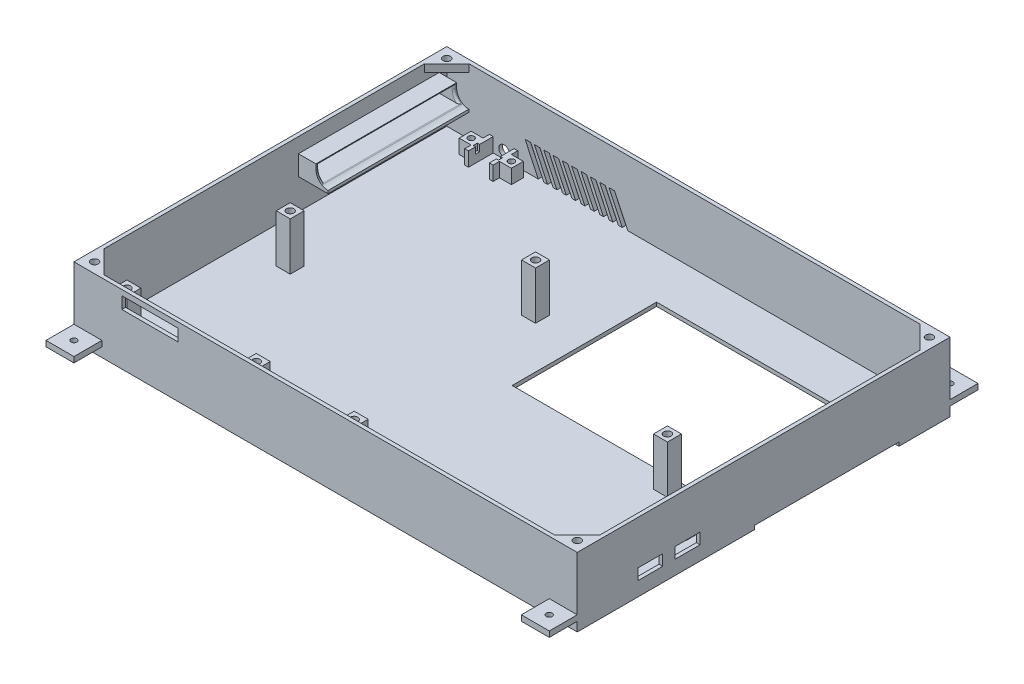
SolidWorks part; units mm, degrees
material "PLA"
ref_plane "Спереди" through (0, 0, 0) normal (0, 0, 1) x (1, 0, 0)
ref_plane "Сверху" through (0, 0, 0) normal (0, 1, 0) x (1, 0, 0)
ref_plane "Справа" through (0, 0, 0) normal (1, 0, 0) x (0, 0, -1)
sketch "Эскиз1" plane through (0, 0, 0) normal (0, 1, 0) x (1, 0, 0)
  line L1 (135, 100) -> (-135, 100)
  line L2 (135, 100) -> (135, -100)
  line L3 (135, -100) -> (-135, -100)
  line L4 (-135, 100) -> (-135, -100)
  line L5 (135, 100) -> (-135, -100) construction
  line L6 (135, -100) -> (-135, 100) construction
  point P0 (0, 0)
  dimension "D1" = 200
  dimension "D2" = 270
extrude "Бобышка-Вытянуть1" add sketch "Эскиз1" along normal blind 2
sketch "Эскиз2" plane through (0, 2, 0) normal (0, 1, 0) x (1, 0, 0)
  line L0 (133, 98) -> (-133, 98)
  line L1 (-133, 98) -> (-133, -98)
  line L2 (-133, -98) -> (-109.3, -98)
  line L3 (133, -98) -> (133, 98)
  line L4 (-135, 100) -> (-135, -100)
  line L5 (-135, -100) -> (135, -100)
  line L6 (135, -100) -> (135, 100)
  line L7 (135, 100) -> (-135, 100)
  line L8 (-135, 100) -> (-135, -100)
  line L9 (-135, -100) -> (-109.3, -100)
  line L10 (135, -100) -> (135, 100)
  line L11 (135, 100) -> (-135, 100)
  line L12 (-109.3, -98) -> (-109.3, -100)
  line L14 (-79.1, -98) -> (-79.1, -100)
  line L16 (-79.1, -98) -> (133, -98)
  line L17 (-79.1, -100) -> (135, -100)
  line L18 (-133, -98) -> (133, -98) construction
  line L20 (-135, -100) -> (135, -100) construction
  dimension "D3" = 25.7
  dimension "D4" = 55.9
  dimension "D1" = 0
  dimension "D2" = 2
extrude "Бобышка-Вытянуть2" add sketch "Эскиз2" along normal offset from surface (35 mm away) 8 offset beyond the face yes
sketch "Эскиз3" plane through (0, 2, 0) normal (0, 1, 0) x (1, 0, 0)
  line L1 (-109.3, -98) -> (-79.1, -98)
  line L2 (-109.3, -98) -> (-109.3, -100)
  line L3 (-109.3, -100) -> (-79.1, -100)
  line L4 (-79.1, -98) -> (-79.1, -100)
extrude "Бобышка-Вытянуть3" add sketch "Эскиз3" along normal blind 25.7
sketch "Эскиз4" plane through (-109.3, 0, 0) normal (1, 0, 0) x (0, 0, -1)
  line L0 (-100, 37) -> (-100, 27.7) construction
  line L1 (-98, 37) -> (-100, 37)
  line L2 (-98, 37) -> (-98, 34.1)
  line L3 (-98, 34.1) -> (-100, 34.1)
  line L4 (-100, 37) -> (-100, 34.1)
  dimension "D1" = 2.9
extrude "Бобышка-Вытянуть4" add sketch "Эскиз4" along normal up to surface (30.2 mm away) up to face at (-79.1, 32.35, 99)
sketch "Эскиз5" plane through (135, 0, 0) normal (1, 0, 0) x (0, 0, -1)
  line L0 (-100, 37) -> (-100, 0) construction
  line L1 (-54.15, 13.5) -> (-67.45, 13.5)
  line L2 (-54.15, 13.5) -> (-54.15, 7.6)
  line L3 (-54.15, 7.6) -> (-67.45, 7.6)
  line L4 (-67.45, 13.5) -> (-67.45, 7.6)
  line L5 (-54.15, 13.5) -> (-67.45, 7.6) construction
  line L6 (-54.15, 7.6) -> (-67.45, 13.5) construction
  line L7 (-34.15, 13.5) -> (-47.45, 13.5)
  line L8 (-34.15, 13.5) -> (-34.15, 7.6)
  line L9 (-34.15, 7.6) -> (-47.45, 7.6)
  line L10 (-47.45, 13.5) -> (-47.45, 7.6)
  line L11 (-34.15, 13.5) -> (-47.45, 7.6) construction
  line L12 (-34.15, 7.6) -> (-47.45, 13.5) construction
  line L13 (-100, 0) -> (100, 0) construction
  point P0 (-60.8, 10.55)
  point P5 (-40.8, 10.55)
  dimension "D1" = 13.3
  dimension "D2" = 5.9
  dimension "D3" = 6.7
  dimension "D4" = 32.55
  dimension "D5" = 13.5
extrude "Вырез-Вытянуть1" cut sketch "Эскиз5" against normal up to surface (2 mm away) up to face at (133, 19.5, 0)
sketch "Эскиз10" plane through (0, 2, 0) normal (0, 1, 0) x (1, 0, 0)
  line L0 (133, 98) -> (133, -98) construction
  line L1 (123.675, -22.825) -> (116.175, -22.825)
  line L2 (123.675, -22.825) -> (123.675, -30.325)
  line L3 (123.675, -30.325) -> (116.175, -30.325)
  line L4 (116.175, -22.825) -> (116.175, -30.325)
  line L5 (123.675, -22.825) -> (116.175, -30.325) construction
  line L6 (123.675, -30.325) -> (116.175, -22.825) construction
  line L7 (114.05, -54.9) -> (106.55, -54.9)
  line L8 (114.05, -54.9) -> (114.05, -62.4)
  line L9 (114.05, -62.4) -> (106.55, -62.4)
  line L10 (106.55, -54.9) -> (106.55, -62.4)
  line L11 (114.05, -54.9) -> (106.55, -62.4) construction
  line L12 (114.05, -62.4) -> (106.55, -54.9) construction
  line L13 (114.675, -87.875) -> (107.175, -87.875)
  line L14 (114.675, -87.875) -> (114.675, -95.375)
  line L15 (114.675, -95.375) -> (107.175, -95.375)
  line L16 (107.175, -87.875) -> (107.175, -95.375)
  line L17 (114.675, -87.875) -> (107.175, -95.375) construction
  line L18 (114.675, -95.375) -> (107.175, -87.875) construction
  line L19 (133, -98) -> (-133, -98) construction
  point P0 (119.925, -26.575)
  point P5 (110.3, -58.65)
  point P10 (110.925, -91.625)
  dimension "D1" = 13.075
  dimension "D2" = 71.425
  dimension "D3" = 22.7
  dimension "D4" = 39.35
  dimension "D5" = 22.075
  dimension "D6" = 6.375
  dimension "D7" = 7.5
extrude "Бобышка-Вытянуть6" add sketch "Эскиз10" along normal blind 6.9
sketch "Эскиз11" plane through (0, 2, 0) normal (0, 1, 0) x (1, 0, 0)
  line L1 (-45.3446, -84.35) -> (-52.8446, -84.35)
  line L2 (-45.3446, -84.35) -> (-45.3446, -91.85)
  line L3 (-45.3446, -91.85) -> (-52.8446, -91.85)
  line L4 (-52.8446, -84.35) -> (-52.8446, -91.85)
  line L5 (-45.3446, -84.35) -> (-52.8446, -91.85) construction
  line L6 (-45.3446, -91.85) -> (-52.8446, -84.35) construction
  line L7 (-17.6224, 30.2491) -> (-25.1224, 30.2491)
  line L8 (-17.6224, 30.2491) -> (-17.6224, 37.7491)
  line L9 (-17.6224, 37.7491) -> (-25.1224, 37.7491)
  line L10 (-25.1224, 30.2491) -> (-25.1224, 37.7491)
  line L11 (-17.6224, 30.2491) -> (-25.1224, 37.7491) construction
  line L12 (-17.6224, 37.7491) -> (-25.1224, 30.2491) construction
  line L13 (-114.1446, -92.4424) -> (-121.6446, -92.4424)
  line L14 (-114.1446, -92.4424) -> (-114.1446, -84.9424)
  line L15 (-114.1446, -84.9424) -> (-121.6446, -84.9424)
  line L16 (-121.6446, -92.4424) -> (-121.6446, -84.9424)
  line L17 (-114.1446, -92.4424) -> (-121.6446, -84.9424) construction
  line L18 (-114.1446, -84.9424) -> (-121.6446, -92.4424) construction
  line L19 (-106.25, -12.7324) -> (-113.75, -12.7324)
  line L20 (-106.25, -12.7324) -> (-106.25, -5.2324)
  line L21 (-106.25, -5.2324) -> (-113.75, -5.2324)
  line L22 (-113.75, -12.7324) -> (-113.75, -5.2324)
  line L23 (-106.25, -12.7324) -> (-113.75, -5.2324) construction
  line L24 (-106.25, -5.2324) -> (-113.75, -12.7324) construction
  line L25 (98.6279, -15.2195) -> (91.1279, -15.2195)
  line L26 (98.6279, -15.2195) -> (98.6279, -7.7196)
  line L27 (98.6279, -7.7196) -> (91.1279, -7.7196)
  line L28 (91.1279, -15.2195) -> (91.1279, -7.7196)
  line L29 (98.6279, -15.2195) -> (91.1279, -7.7196) construction
  line L30 (98.6279, -7.7196) -> (91.1279, -15.2195) construction
  line L31 (95.4554, -96.6196) -> (87.9554, -96.6196)
  line L32 (95.4554, -96.6196) -> (95.4554, -89.1196)
  line L33 (95.4554, -89.1196) -> (87.9554, -89.1196)
  line L34 (87.9554, -96.6196) -> (87.9554, -89.1196)
  line L35 (95.4554, -96.6196) -> (87.9554, -89.1196) construction
  line L36 (95.4554, -89.1196) -> (87.9554, -96.6196) construction
  line L37 (7.7554, -92.4285) -> (0.2554, -92.4285)
  line L38 (7.7554, -92.4285) -> (7.7554, -84.9285)
  line L39 (7.7554, -84.9285) -> (0.2554, -84.9285)
  line L40 (0.2554, -92.4285) -> (0.2554, -84.9285)
  line L41 (7.7554, -92.4285) -> (0.2554, -84.9285) construction
  line L42 (7.7554, -84.9285) -> (0.2554, -92.4285) construction
  line L44 (-133, 98) -> (133, 98) construction
  line L45 (-133, -98) -> (-133, 98) construction
  line L47 (133, -98) -> (-133, -98) construction
  line L48 (133, 98) -> (133, -98) construction
  point P0 (-49.0946, -88.1)
  point P5 (-21.3724, 33.9991)
  point P10 (-117.8946, -88.6924)
  point P15 (-110, -8.9824)
  point P20 (94.8779, -11.4695)
  point P25 (91.7054, -92.8696)
  point P30 (4.0054, -88.6785)
  dimension "D1" = 7.5
  dimension "D2" = 64.0009
  dimension "D3" = 111.6276
  dimension "D4" = 106.9824
  dimension "D5" = 23
  dimension "D6" = 9.3076
  dimension "D7" = 15.1054
  dimension "D8" = 9.3215
  dimension "D9" = 128.9946
  dimension "D10" = 9.9
  dimension "D11" = 83.9054
  dimension "D12" = 5.1304
  dimension "D13" = 41.2946
  dimension "D14" = 86.5305
  dimension "D15" = 38.1221
extrude "Бобышка-Вытянуть7" add sketch "Эскиз11" along normal blind 25.7
sketch "Эскиз12" plane through (0, 2, 0) normal (0, 1, 0) x (1, 0, 0)
  line L0 (5, -4.925) -> (135, 72.575) construction
  line L1 (135, 72.575) -> (5, 72.575)
  line L2 (135, 72.575) -> (135, -4.925)
  line L3 (135, -4.925) -> (5, -4.925)
  line L4 (5, 72.575) -> (5, -4.925)
  line L6 (135, -100) -> (135, 100) construction
  line L7 (5, 72.575) -> (135, -4.925) construction
  line L8 (-133, 98) -> (133, 98) construction
  point P4 (70, 33.825)
  dimension "D1" = 64.175
  dimension "D2" = 130
  dimension "D3" = 77.5
extrude "Вырез-Вытянуть2" cut sketch "Эскиз12" against normal through all
sketch "Эскиз30" plane through (0, 2, 0) normal (0, -1, 0) x (1, 0, 0)
  line L4 (133, 4.925) -> (133, -72.575)
  line L5 (133, 4.925) -> (133, -72.575)
  line L6 (133, -72.575) -> (135, -72.575)
  line L7 (135, 4.925) -> (133, 4.925)
  line L11 (135, 4.925) -> (133, 4.925)
  line L12 (133, -72.575) -> (135, -72.575)
  line L13 (135, -72.575) -> (135, 4.925)
  line L14 (135, -72.575) -> (135, 4.925)
  dimension "D1" = 0
extrude "Бобышка-Вытянуть14" add sketch "Эскиз30" along normal up to surface (2 mm away) up to face at (35, 0, -16.9125)
sketch "Эскиз14" plane through (0, 27.7, 0) normal (0, 1, 0) x (1, 0, 0)
  line L0 (-113.75, -5.2324) -> (-106.25, -12.7324) construction
  line L1 (-106.25, -5.2324) -> (-113.75, -12.7324) construction
  line L2 (-17.6224, 37.7491) -> (-25.1224, 30.2491) construction
  line L3 (-25.1224, 37.7491) -> (-17.6224, 30.2491) construction
  line L4 (-121.6446, -84.9424) -> (-114.1446, -92.4424) construction
  line L5 (-114.1446, -84.9424) -> (-121.6446, -92.4424) construction
  line L6 (-52.8446, -84.35) -> (-45.3446, -91.85) construction
  line L7 (-45.3446, -84.35) -> (-52.8446, -91.85) construction
  line L8 (0.2554, -84.9285) -> (7.7554, -92.4285) construction
  line L9 (7.7554, -84.9285) -> (0.2554, -92.4285) construction
  line L10 (95.4554, -89.1196) -> (87.9554, -96.6196) construction
  line L11 (95.4554, -89.1196) -> (87.9554, -89.1196) construction
  line L12 (95.4554, -89.1196) -> (95.4554, -96.6196) construction
  line L13 (95.4554, -96.6196) -> (87.9554, -96.6196) construction
  line L14 (87.9554, -89.1196) -> (87.9554, -96.6196) construction
  line L15 (95.4554, -96.6196) -> (87.9554, -89.1196) construction
  line L22 (98.6279, -7.7196) -> (91.1279, -15.2195) construction
  line L23 (98.6279, -15.2195) -> (91.1279, -7.7196) construction
  circle A0 centre (-21.3724, 33.9991) radius 2
  circle A1 centre (-110, -8.9824) radius 2
  circle A2 centre (-117.8946, -88.6924) radius 2
  circle A3 centre (-49.0946, -88.1) radius 2
  circle A4 centre (4.0054, -88.6785) radius 2
  circle A5 centre (91.7054, -92.8696) radius 2
  circle A6 centre (94.8779, -11.4695) radius 2
  dimension "D1" = 4
extrude "Вырез-Вытянуть4" cut sketch "Эскиз14" against normal blind 5
sketch "Эскиз15" plane through (0, 8.9, 0) normal (0, 1, 0) x (1, 0, 0)
  line L0 (123.675, -22.825) -> (116.175, -30.325) construction
  line L1 (116.175, -22.825) -> (123.675, -30.325) construction
  line L2 (106.55, -54.9) -> (114.05, -62.4) construction
  line L3 (114.05, -54.9) -> (106.55, -62.4) construction
  line L4 (107.175, -87.875) -> (114.675, -95.375) construction
  line L5 (114.675, -87.875) -> (107.175, -95.375) construction
  circle A0 centre (110.925, -91.625) radius 2
  circle A1 centre (110.3, -58.65) radius 2
  circle A2 centre (119.925, -26.575) radius 2
  dimension "D1" = 4
extrude "Вырез-Вытянуть5" cut sketch "Эскиз15" against normal blind 5
sketch "Эскиз16" plane through (0, 0, -100) normal (0, 0, -1) x (-1, 0, 0)
  line L0 (133, 29) -> (123.6, 29)
  line L1 (133, 37) -> (133, 2) construction
  line L2 (123.6, 29) -> (123.6, 26.4)
  line L3 (117.1, 19.9) -> (133, 19.9)
  line L4 (133, 19.9) -> (133, 29)
  line L5 (133, 2) -> (-133, 2) construction
  arc A0 (123.6, 26.4) -> (117.1, 19.9) centre (117.1, 26.4) cw
  dimension "D3" = 6.5
  dimension "D1" = 9.4
  dimension "D2" = 2.6
  dimension "D4" = 27
  dimension "D5" = 15.9
extrude "Бобышка-Вытянуть8" add sketch "Эскиз16" against normal blind 75.5 from offset 6.0824 offset against normal yes
sketch "Эскиз18" plane through (0, 0, -18.4176) normal (0, 0, 1) x (1, 0, 0)
  line L0 (-135, 28) -> (-123.6, 28)
  line L1 (-135, 37) -> (-135, 0) construction
  line L2 (-123.6, 29) -> (-123.6, 26.4) construction
  line L3 (-123.6, 28) -> (-123.6, 26.4)
  line L4 (-135, 28) -> (-135, 20.9)
  line L5 (-135, 20.9) -> (-120.5641, 20.9)
  line L6 (-133, 29) -> (-123.6, 29) construction
  line L7 (-117.1, 19.9) -> (-133, 19.9) construction
  arc A0 (-123.6, 26.4) -> (-117.1, 19.9) centre (-117.1, 26.4) ccw construction
  arc A1 (-123.6, 26.4) -> (-120.5641, 20.9) centre (-117.1, 26.4) ccw
  dimension "D1" = 1
  dimension "D2" = 1
extrude "Вырез-Вытянуть6" cut sketch "Эскиз18" against normal offset from surface (72.5 mm away) 1.5 from offset 1.5 up to face at (-126.3292, 24.5708, -93.9176) offset against normal yes
fillet "Скругление1" radius 1 6 edges at (-123.6, 27.2, -92.4176) (-123.6, 27.2, -19.9176) (-122.7906, 23.2589, -92.4176) (-120.5641, 20.9, -56.1676) (-122.7906, 23.2589, -19.9176) (-123.6, 28, -56.1676)
sketch "Эскиз19" plane through (0, 0, -18.4176) normal (0, 0, 1) x (1, 0, 0)
  line L0 (-133, 19.9) -> (-133, 18.4)
  line L1 (-133, 37) -> (-133, 2) construction
  line L2 (-133, 19.9) -> (-117.1, 19.9)
  line L3 (-117.1, 19.9) -> (-133, 19.9) construction
  line L4 (-117.1, 19.9) -> (-117.1, 18.4)
  line L5 (-117.1, 18.4) -> (-133, 18.4)
  dimension "D1" = 1.5
extrude "Бобышка-Вытянуть9" add sketch "Эскиз19" against normal up to surface (75.5 mm away) up to face at (-126.3292, 24.5708, -93.9176)
sketch "Эскиз20" plane through (0, 0, -100) normal (0, 0, -1) x (-1, 0, 0)
  line L0 (135, 37) -> (135, 0) construction
  line L1 (90.9881, 17) -> (87.9881, 17)
  line L3 (83.9, 2) -> (80.9, 2)
  line L5 (90.9, 17) -> (35.9, 2) construction
  line L6 (90.9, 2) -> (35.9, 17) construction
  line L7 (-135, 0) -> (135, 0) construction
  line L8 (35.9, 2) -> (42.9881, 17)
  line L9 (45.9881, 17) -> (38.9, 2)
  line L10 (40.9, 2) -> (47.9881, 17)
  line L11 (50.9881, 17) -> (43.9, 2)
  line L12 (45.9, 2) -> (52.9881, 17)
  line L13 (55.9881, 17) -> (48.9, 2)
  line L14 (50.9, 2) -> (57.9881, 17)
  line L15 (60.9881, 17) -> (53.9, 2)
  line L16 (55.9, 2) -> (62.9881, 17)
  line L17 (65.9881, 17) -> (58.9, 2)
  line L18 (60.9, 2) -> (67.9881, 17)
  line L19 (70.9881, 17) -> (63.9, 2)
  line L20 (65.9, 2) -> (72.9881, 17)
  line L21 (75.9881, 17) -> (68.9, 2)
  line L22 (70.9, 2) -> (77.9881, 17)
  line L23 (80.9881, 17) -> (73.9, 2)
  line L24 (75.9, 2) -> (82.9881, 17)
  line L25 (85.9881, 17) -> (78.9, 2)
  line L26 (80.9, 2) -> (87.9881, 17)
  line L27 (90.9881, 17) -> (83.9, 2)
  line L28 (45.9881, 17) -> (42.9881, 17)
  line L29 (38.9, 2) -> (35.9, 2)
  line L30 (43.9, 2) -> (40.9, 2)
  line L31 (50.9881, 17) -> (47.9881, 17)
  line L32 (55.9881, 17) -> (52.9881, 17)
  line L33 (48.9, 2) -> (45.9, 2)
  line L34 (53.9, 2) -> (50.9, 2)
  line L35 (60.9881, 17) -> (57.9881, 17)
  line L36 (58.9, 2) -> (55.9, 2)
  line L37 (65.9881, 17) -> (62.9881, 17)
  line L38 (63.9, 2) -> (60.9, 2)
  line L39 (70.9881, 17) -> (67.9881, 17)
  line L40 (68.9, 2) -> (65.9, 2)
  line L41 (75.9881, 17) -> (72.9881, 17)
  line L42 (73.9, 2) -> (70.9, 2)
  line L43 (80.9881, 17) -> (77.9881, 17)
  line L44 (78.9, 2) -> (75.9, 2)
  line L45 (85.9881, 17) -> (82.9881, 17)
  line L46 (35.9, 17) -> (35.9, 2) construction
  line L47 (90.9, 17) -> (90.9, 2) construction
  point P0 (63.4, 9.5)
  dimension "D1" = 71.6
  dimension "D2" = 2
  dimension "D3" = 15
  dimension "D4" = 55
  dimension "D5" = 3
  dimension "D8" = 2
  dimension "D9" = 64.707
  dimension "D6" = 10
extrude "Вырез-Вытянуть7" cut sketch "Эскиз20" against normal up to surface (2 mm away) up to face at (0, 19.5, -98)
sketch "Эскиз21" plane through (0, 0, -100) normal (0, 0, -1) x (-1, 0, 0)
  line L0 (135, 37) -> (135, 0) construction
  line L1 (-135, 0) -> (135, 0) construction
  circle A0 centre (102.2, 5.825) radius 2.9
  dimension "D1" = 5.8
  dimension "D2" = 32.8
  dimension "D3" = 5.825
extrude "Вырез-Вытянуть8" cut sketch "Эскиз21" against normal up to surface (2 mm away) up to face at (-57.6764, 10.4091, -98)
sketch "Эскиз22" plane through (0, 2, 0) normal (0, 1, 0) x (1, 0, 0)
  line L0 (-133, 98) -> (-83.9, 98) construction
  line L1 (-108.1, 98) -> (-110.1, 98)
  line L2 (-108.1, 98) -> (-108.1, 84.75)
  line L3 (-108.1, 84.75) -> (-110.1, 84.75)
  line L4 (-110.1, 98) -> (-110.1, 84.75)
  line L5 (-133, -98) -> (-133, 98) construction
  line L7 (-94.9, 98) -> (-96.9, 98)
  line L8 (-94.9, 98) -> (-94.9, 84.75)
  line L9 (-94.9, 84.75) -> (-96.9, 84.75)
  line L10 (-96.9, 98) -> (-96.9, 84.75)
  dimension "D1" = 24.9
  dimension "D2" = 13.25
  dimension "D3" = 2
  dimension "D4" = 36.1
extrude "Бобышка-Вытянуть10" add sketch "Эскиз22" along normal blind 7.65
sketch "Эскиз23" plane through (0, 9.65, 0) normal (0, 1, 0) x (1, 0, 0)
  line L0 (-108.1, 84.75) -> (-108.1, 98) construction
  line L1 (-108.1, 90.7) -> (-109.3, 90.7)
  line L2 (-108.1, 90.7) -> (-108.1, 88.5)
  line L3 (-108.1, 88.5) -> (-109.3, 88.5)
  line L4 (-109.3, 90.7) -> (-109.3, 88.5)
  line L5 (-96.9, 98) -> (-96.9, 84.75) construction
  line L6 (-96.9, 90.7) -> (-95.7, 90.7)
  line L7 (-96.9, 90.7) -> (-96.9, 88.5)
  line L8 (-96.9, 88.5) -> (-95.7, 88.5)
  line L9 (-95.7, 90.7) -> (-95.7, 88.5)
  line L10 (-110.1, 84.75) -> (-108.1, 84.75) construction
  dimension "D1" = 2.2
  dimension "D2" = 1.2
  dimension "D3" = 5.95
extrude "Вырез-Вытянуть9" cut sketch "Эскиз23" against normal blind 3.45
sketch "Эскиз24" plane through (0, 2, 0) normal (0, 1, 0) x (1, 0, 0)
  line L0 (-108.6, 91.375) -> (-97.4, 91.375) construction
  line L3 (-102.5, 91.875) -> (-102.5, 50091.875) construction
  line L4 (-108.1, 84.75) -> (-108.1, 98) construction
  line L5 (-108.1, 98) -> (-96.9, 98) construction
  line L6 (-110.1, 98) -> (-110.1, 84.75) construction
  line L7 (-116.5, 94.575) -> (-110.1, 94.575)
  line L8 (-116.5, 94.575) -> (-116.5, 88.175)
  line L9 (-116.5, 88.175) -> (-110.1, 88.175)
  line L10 (-110.1, 94.575) -> (-110.1, 88.175)
  line L11 (-116.5, 94.575) -> (-110.1, 88.175) construction
  line L12 (-116.5, 88.175) -> (-110.1, 94.575) construction
  line L13 (-88.5, 88.175) -> (-94.9, 88.175)
  line L14 (-94.9, 94.575) -> (-94.9, 88.175)
  line L15 (-88.5, 94.575) -> (-94.9, 94.575)
  line L16 (-88.5, 94.575) -> (-88.5, 88.175)
  circle A0 centre (-113.3, 91.375) radius 1.7 construction
  point P3 (-108.1, 91.375)
  point P8 (-102.5, 98)
  point P10 (-113.3, 91.375)
  dimension "D1" = 3.4
  dimension "D2" = 1.5
extrude "Бобышка-Вытянуть11" add sketch "Эскиз24" along normal up to surface (7.65 mm away) up to face at (-108.9, 9.65, -90.4875)
sketch "Эскиз25" plane through (0, 9.65, 0) normal (0, 1, 0) x (1, 0, 0)
  line L0 (-116.5, 94.575) -> (-110.1, 88.175) construction
  line L1 (-110.1, 94.575) -> (-116.5, 88.175) construction
  line L2 (-94.9, 94.575) -> (-88.5, 88.175) construction
  line L3 (-88.5, 94.575) -> (-94.9, 88.175) construction
  circle A0 centre (-113.3, 91.375) radius 1.65
  circle A1 centre (-91.7, 91.375) radius 1.65
  dimension "D1" = 3.3
extrude "Вырез-Вытянуть10" cut sketch "Эскиз25" against normal blind 3
sketch "Эскиз26" plane through (0, 37, 0) normal (0, 1, 0) x (1, 0, 0)
  line L0 (0, 0) -> (0, 50000) construction
  line L1 (0, 0) -> (-50000, 0) construction
  line L2 (121, 98) -> (133, 98)
  line L3 (-35.9, 98) -> (133, 98) construction
  line L4 (133, 98) -> (133, 86)
  line L5 (133, 98) -> (133, -98) construction
  line L6 (133, 86) -> (121, 98)
  line L7 (133, 98) -> (127, 92) construction
  line L8 (133, -98) -> (133, -86)
  line L9 (121, -98) -> (133, -98)
  line L10 (133, -86) -> (121, -98)
  line L11 (-121, -98) -> (-133, -98)
  line L12 (-133, -86) -> (-121, -98)
  line L13 (-133, -98) -> (-133, -86)
  line L14 (-133, 98) -> (-133, 86)
  line L15 (-121, 98) -> (-133, 98)
  line L16 (-133, 86) -> (-121, 98)
  circle A0 centre (129.5102, 94.5102) radius 2.05 construction
  dimension "D1" = 4.1
  dimension "D3" = 1.5
  dimension "D4" = 1.4398
  dimension "D2" = 12
extrude "Бобышка-Вытянуть12" add sketch "Эскиз26" against normal blind 4
sketch "Эскиз27" plane through (0, 37, 0) normal (0, 1, 0) x (1, 0, 0)
  line L0 (0, 0) -> (0, 50000) construction
  line L1 (0, 0) -> (-50000, 0) construction
  line L2 (135, 100) -> (127, 92) construction
  line L3 (121, 98) -> (133, 86) construction
  circle A0 centre (129.4749, 94.4749) radius 2
  circle A1 centre (129.4749, -94.4749) radius 2
  circle A2 centre (-129.4749, -94.4749) radius 2
  circle A3 centre (-129.4749, 94.4749) radius 2
  dimension "D1" = 4
  dimension "D2" = 1.5
extrude "Вырез-Вытянуть11" cut sketch "Эскиз27" against normal up to surface (4 mm away) up to face at (129, 33, -94)
sketch "Эскиз28" plane through (0, 0, -100) normal (0, 0, -1) x (-1, 0, 0)
  line L0 (-135, 37) -> (-135, 0) construction
  line L1 (-135, 5) -> (-120, 5)
  line L2 (-135, 5) -> (-135, 8)
  line L3 (-135, 8) -> (-120, 8)
  line L4 (-120, 5) -> (-120, 8)
  line L5 (-135, 0) -> (135, 0) construction
  dimension "D1" = 3
  dimension "D2" = 15
  dimension "D3" = 5
extrude "Бобышка-Вытянуть13" add sketch "Эскиз28" along normal blind 15
sketch "Эскиз29" plane through (0, 8, 0) normal (0, 1, 0) x (1, 0, 0)
  line L0 (120, 115) -> (135, 100) construction
  line L1 (135, 115) -> (120, 100) construction
  circle A0 centre (127.5, 107.5) radius 1.6
  dimension "D1" = 3.2
extrude "Вырез-Вытянуть12" cut sketch "Эскиз29" against normal through all
mirror "Зеркальное отражение1" about plane through (0, 0, 0) normal (0, 0, 1) of "Вырез-Вытянуть12", "Бобышка-Вытянуть13"
mirror "Зеркальное отражение2" about plane through (0, 0, 0) normal (1, 0, 0) of "Зеркальное отражение1"
sketch "Эскиз31" plane through (133, 0, 0) normal (-1, 0, 0) x (0, 0, 1)
  line L1 (4.925, 0) -> (-72.575, 0)
  line L2 (4.925, 0) -> (4.925, 2)
  line L3 (4.925, 2) -> (-72.575, 2)
  line L4 (-72.575, 0) -> (-72.575, 2)
extrude "Вырез-Вытянуть13" cut sketch "Эскиз31" against normal up to surface (2 mm away) up to face at (135, 10.5, 0)
